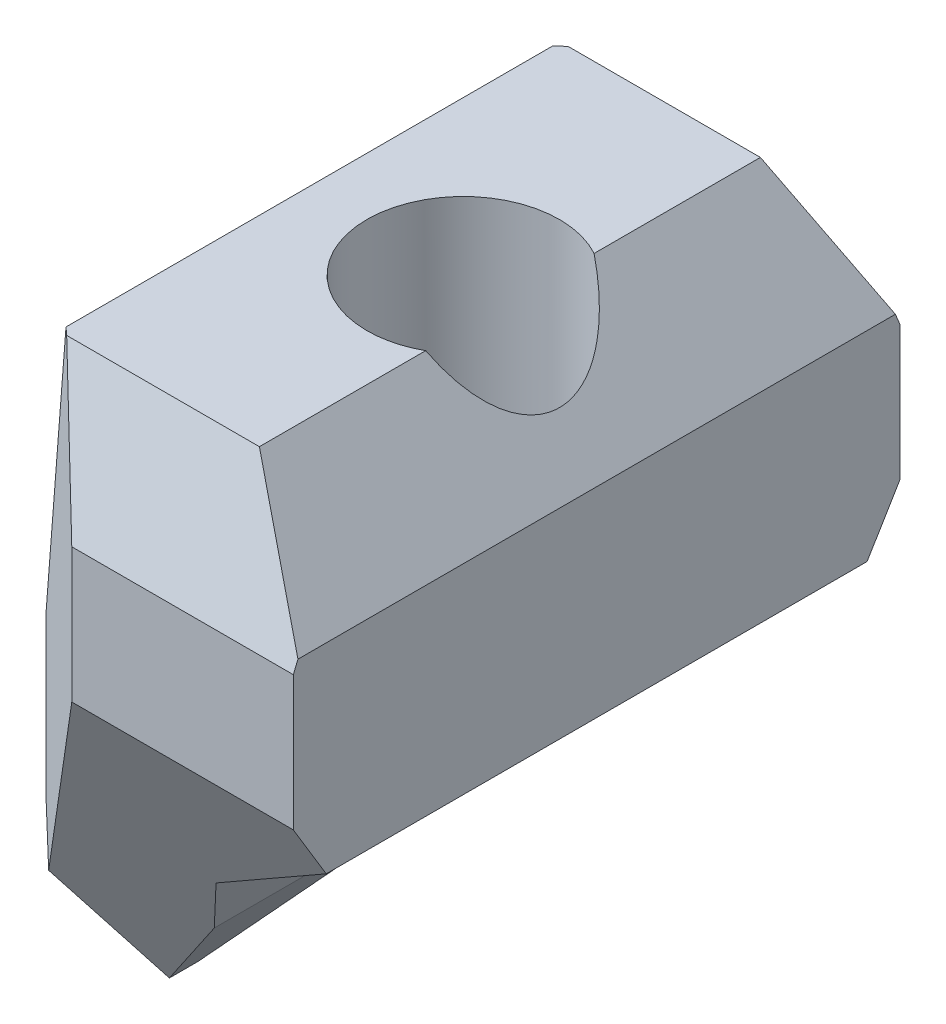
SolidWorks part; units mm, degrees
ref_plane "Front Plane" through (0, 0, 0) normal (0, 0, 1) x (1, 0, 0)
ref_plane "Top Plane" through (0, 0, 0) normal (0, 1, 0) x (1, 0, 0)
ref_plane "Right Plane" through (0, 0, 0) normal (1, 0, 0) x (0, 0, -1)
sketch3d "3DSketch2"
  point P0 (-117.438, 78.016, 41.845)
  point P1 (-119.873, 74.978, 44.514)
  point P2 (-92.88, 68.104, 41.63)
  point P3 (-93.749, 64.434, 44.285)
  point P4 (-87.502, 65.933, 14.17)
  point P5 (-88.506, 59.611, 15.582)
  point P6 (-100.269, 49.439, 46.938)
  point P7 (-89.636, 50.559, 17.809)
  point P8 (-91.154, 45.295, 18.536)
  point P10 (-93.05, 39.799, 19.093)
  point P11 (-91.732, 32.772, 22.26)
  point P13 (-106.924, 36.507, 46.38)
  point P15 (-92.168, 27.46, 23.715)
  point P16 (-95.793, 23.202, 22.731)
  point P17 (-111.593, 30.506, 41.77)
  point P18 (-89.33, 33.272, -0.262)
  point P19 (-115.16, 28.235, 35.065)
  point P20 (-104.983, 21.112, 17.38)
  point P21 (-92.513, 27.599, -24.239)
  point P22 (-105.368, 29.386, -0.16)
  point P23 (-92.055, 32.903, -22.751)
  point P24 (-93.327, 39.911, -19.514)
  point P25 (-91.423, 45.403, -18.945)
  point P26 (-89.895, 50.662, -18.202)
  point P27 (-135.845, 36.584, 35.246)
  point P28 (-136.231, 40.45, 41.986)
  point P29 (-134.283, 47.551, 46.62)
  point P30 (-119.482, 20.083, 34.366)
  point P31 (-139.753, 28.267, 34.543)
  point P32 (-141.848, 21.844, 31.314)
  point P33 (-155.529, 31.464, 19.864)
  point P34 (-115.167, 24.836, -0.105)
  point P35 (-153.668, 37.129, 20.521)
  point P36 (-147.549, 42.545, 18.202)
  point P37 (-144.275, 49.109, 18.202)
  point P38 (-143.24, 56.733, 20.083)
  point P39 (-90.675, 55.615, -0.171)
  point P40 (-133.878, 65.168, 16.582)
  point P41 (-99.288, 59.866, -0.094)
  point P42 (-103.11, 62.801, -0.055)
  point P43 (-94.881, 61.953, -0.118)
  point P44 (-118.386, 61.08, 0.05)
  point P45 (-135.318, 50.905, 0.137)
  point P46 (-146.728, 43.45, 0.192)
  point P47 (-96.122, 23.334, -23.234)
  point P48 (-159.215, 32.873, 0.246)
  point P49 (-127.076, 23.767, -0.022)
  point P50 (-87.708, 66.016, -14.482)
  point P51 (-127.957, 60.614, 47.182)
  point P52 (-88.732, 59.704, -15.926)
  point P53 (-101.06, 71.406, -0.038)
  point P54 (-105.266, 73.567, 0)
  point P55 (-111.968, 74.262, 0.051)
  point P56 (-128.867, 75.593, 16.714)
  point P57 (-124.12, 79.94, 14.964)
  point P58 (-118.3, 68.313, 0.075)
  point P59 (-93.479, 68.346, -41.845)
  point P60 (-94.386, 64.69, -44.514)
  point P61 (-124.333, 80.026, -14.642)
  point P62 (-129.105, 75.689, -16.353)
  point P63 (-118.037, 78.258, -41.63)
  point P64 (-120.51, 75.235, -44.285)
  point P65 (-134.112, 65.263, -16.225)
  point P66 (-133.247, 58.266, 0.148)
  point P67 (-128.634, 60.888, -46.938)
  point P68 (-143.525, 56.847, -19.649)
  point P69 (-144.531, 49.215, -17.809)
  point P70 (-134.952, 47.82, -46.38)
  point P71 (-156.903, 41.682, 0.261)
  point P72 (-147.808, 42.65, -17.809)
  point P73 (-136.834, 40.695, -41.77)
  point P74 (-160.282, 37.48, 0.27)
  point P75 (-136.349, 36.788, -35.065)
  point P76 (-153.917, 26.56, 17.108)
  point P77 (-112.193, 30.748, -41.986)
  point P78 (-107.592, 36.777, -46.62)
  point P79 (-115.664, 28.44, -35.246)
  point P80 (-141.958, 17.558, 25.417)
  point P81 (-113.098, 14.879, -14.57)
  point P82 (-121.302, 8.912, 10.659)
  point P83 (-127.042, 11.539, 25.286)
  point P84 (-112.892, 14.795, 14.255)
  point P85 (-123.47, 14.427, 31.153)
  point P86 (-105.235, 21.214, -17.765)
  point P87 (-119.977, 20.284, -34.542)
  point P88 (-160.375, 19.813, 19.207)
  point P89 (-140.249, 28.466, -34.366)
  point P90 (-154.159, 26.658, -16.738)
  point P91 (-167.79, 26.284, 0.284)
  point P92 (-155.81, 31.577, -19.436)
  point P93 (-153.958, 37.247, -20.078)
  point P94 (-130.006, 4.076, 27.381)
  point P95 (-121.456, 8.974, -10.894)
  point P96 (-146.158, 10.595, 27.522)
  point P97 (-139.719, 14.799, 0.038)
  point P98 (-123.92, 14.607, -31.314)
  point P99 (-129.428, 4.384, 6.807)
  point P100 (-129.528, 4.424, -6.957)
  point P101 (-127.404, 11.686, -25.417)
  point P102 (-135.742, -3.659, 22.212)
  point P103 (-138.165, -1.368, 2.954)
  point P104 (-130.4, 4.235, -27.522)
  point P105 (-138.208, -1.35, -3.019)
  point P106 (-148.845, 1.629, 22.327)
  point P107 (-150.28, 8.083, 0.09)
  point P108 (-142.322, 17.705, -25.286)
  point P109 (-142.296, 22.024, -31.153)
  point P110 (-161.506, 12.383, 17.458)
  point P111 (-160.648, 19.924, -18.794)
  point P112 (-167.767, 16.378, 0.248)
  point P113 (-169.767, 21.362, 0.281)
  point P114 (-161.877, 5.574, 15.401)
  point P115 (-146.552, 10.754, -27.381)
  point P116 (-152.128, -6.787, 19.659)
  point P117 (-145.949, -4.952, -0.985)
  point P118 (-145.935, -4.957, 1.006)
  point P119 (-136.062, -3.53, -22.327)
  point P120 (-140.59, -11.445, 19.558)
  point P121 (-144.099, -14.511, 14.11)
  point P122 (-147.112, -15.77, 7.543)
  point P123 (-140.872, -11.331, -19.659)
  point P124 (-151.561, -13.974, 7.583)
  point P125 (-152.422, -11.153, 14.182)
  point P126 (-149.165, 1.758, -22.211)
  point P127 (-162.516, 0.034, 13.957)
  point P128 (-164.225, -5.846, 13.126)
  point P129 (-162.094, 5.663, -15.069)
  point P130 (-161.754, 12.483, -17.081)
  point P131 (-171.523, 10.783, 0.254)
  point P132 (-162.713, 0.114, -13.656)
  point P133 (-179.688, 3.407, 0.287)
  point P134 (-174.941, -3.455, 0.227)
  point P135 (-164.412, -5.771, -12.842)
  point P136 (-164.22, -12.033, 11.026)
  point P137 (-152.409, -6.674, -19.558)
  point P138 (-160.832, -7.603, 0.11)
  point P139 (-152.626, -11.07, -14.11)
  point P140 (-159.688, -13.014, 0.082)
  point P141 (-151.669, -13.93, -7.543)
  point P142 (-152.393, -16.035, -1.584)
  point P143 (-152.37, -16.045, 1.619)
  point P144 (-149.6388, -16.8932, 0)
  point P145 (-144.301, -14.431, -14.182)
  point P146 (-150.066, -21.999, 7.962)
  point P147 (-149.741, -19.734, 1.37)
  point P148 (-149.76, -19.726, -1.4)
  point P149 (-157.777, -21.979, 14.042)
  point P150 (-154.765, -20.103, 8.004)
  point P151 (-156.701, -19.629, 14.323)
  point P152 (-149.536, -25.306, 13.97)
  point P153 (-148.296, -23.022, 14.25)
  point P154 (-167.359, -15.87, 11.857)
  point P155 (-152.25, -26.375, 7.962)
  point P156 (-151.942, -25.186, 1.712)
  point P157 (-151.966, -25.175, -1.75)
  point P158 (-148.502, -22.94, -14.323)
  point P159 (-150.182, -21.953, -8.004)
  point P160 (-156.948, -24.478, 8.004)
  point P161 (-154.878, -20.056, -7.962)
  point P162 (-156.907, -19.547, -14.25)
  point P163 (-162.464, -21.788, 0.07)
  point P164 (-169.295, -22.202, 11.026)
  point P165 (-157.978, -21.9, -13.97)
  point P166 (-164.135, -26.062, 6.213)
  point P167 (-157.062, -24.433, -7.962)
  point P168 (-158.939, -30.015, 5.757)
  point P169 (-154.493, -28.561, -1.182)
  point P170 (-154.476, -28.569, 1.156)
  point P171 (-149.738, -25.225, -14.042)
  point P172 (-152.364, -26.328, -8.004)
  point P173 (-155.56, -31.379, 5.727)
  point P174 (-164.223, -26.026, -6.079)
  point P175 (-161.226, -28.937, 0.035)
  point P176 (-164.376, -11.971, -10.788)
  point P177 (-167.527, -15.802, -11.602)
  point P178 (-175.586, -13.09, 0.198)
  point P179 (-169.452, -22.139, -10.788)
  point P180 (-178.071, -23.529, 0.178)
  point P181 (-169.716, -28.294, 0.1)
  point P182 (-165.309, -32.933, 4.682)
  point P183 (-159.814, -34.455, 0.004)
  point P184 (-155.641, -31.345, -5.757)
  point P185 (-156.301, -33.476, -1.619)
  point P186 (-156.278, -33.486, 1.584)
  point P187 (-159.02, -29.982, -5.727)
  point P188 (-165.374, -32.906, -4.58)
  point P189 (-170.651, -36.265, 0.077)
  point P190 (-163.07, -42.263, 0)
  point P191 (-147.22, -15.726, -7.583)
  point P192 (-100.944, 49.711, -47.182)
sketch "Sketch1" plane through (0, 0, 0) normal (1, 0, 0) x (0, 0, -1)
  line L0 (0, -42.263) -> (0, 79.94) construction
  line L5 (-41.294, 79.94) -> (0, 79.94)
  line L6 (-41.294, 79.94) -> (-50, 58.8941)
  line L7 (-50, 58.8941) -> (-50, 36.7381)
  line L8 (-50, 36.7381) -> (-2.3599, -42.263)
  line L9 (-2.3599, -42.263) -> (2.3599, -42.263)
  line L10 (50, 36.7381) -> (2.3599, -42.263)
  line L11 (50, 58.8941) -> (50, 36.7381)
  line L12 (41.294, 79.94) -> (50, 58.8941)
  line L13 (41.294, 79.94) -> (0, 79.94)
  dimension "D1" = 50
extrude "Boss-Extrude1" add sketch "Sketch1" against normal up to vertex (179.688 mm away) from offset 95 up to point (-179.688, 3.407, 0.287) offset against normal yes
sketch "Sketch2" plane through (0, 0, 0) normal (0, 0, 1) x (1, 0, 0)
  line L0 (-142.3339, 79.94) -> (-179.688, 3.407)
  line L2 (-179.688, 3.407) -> (-179.688, -22.8009)
  line L3 (-179.688, 36.7381) -> (-179.688, -42.263) construction
  line L4 (-179.688, -22.8009) -> (-163.07, -42.263)
  line L5 (-163.07, -42.263) -> (-139.1994, -14.9523)
  line L6 (-139.1994, -14.9523) -> (-128.9233, 1.6089)
  line L7 (-128.9233, 1.6089) -> (-95, 27.7558)
  line L8 (-95, 36.7381) -> (-95, -42.263) construction
  line L9 (-95, 27.7558) -> (-95, 60.7245)
  line L10 (-95, 60.7245) -> (-109.3008, 79.94)
  line L12 (-179.688, 79.94) -> (-95, 79.94) construction
  line L13 (-109.3008, 79.94) -> (-142.3339, 79.94)
  line L14 (-95, 79.94) -> (-95, 58.8941) construction
extrude "Cut-Extrude1" cut sketch "Sketch2" against normal through all both and the other way through all flip side to cut
sketch "Sketch3" plane through (0, 0, 0) normal (0, 1, 0) x (1, 0, 0)
  line L1 (-95, 50) -> (-131.5887, 50)
  line L8 (-179.688, -0.287) -> (-95, 0) construction
  line L9 (-95, 49.2428) -> (-95, -49.2428) construction
  line L13 (-179.688, 5.5432) -> (-179.688, -0.287)
  line L25 (-179.6485, -6.117) -> (-179.688, -0.287)
  line L28 (-94.6611, -49.9989) -> (-131.2489, -50.2468)
  line L30 (-95, 50) -> (-95, 0)
  line L31 (-94.6611, -49.9989) -> (-95, 0)
  line L34 (-131.5887, 50) -> (-179.688, 5.5432)
  line L35 (-131.2489, -50.2468) -> (-179.6485, -6.117)
extrude "Cut-Extrude2" cut sketch "Sketch3" against normal through all both and the other way through all flip side to cut
sketch "Sketch5" plane through (0, 0, 0) normal (0, 1, 0) x (1, 0, 0)
  line L0 (-95, 49.2428) -> (-95, -49.2428) construction
  circle A0 centre (-117, 0) radius 15.875
  dimension "D1" = 31.75
  dimension "D2" = 22
extrude "Cut-Extrude4" cut sketch "Sketch5" against normal blind 48 from surface starting at face at (-130.8909, 79.94, 0.0119)
